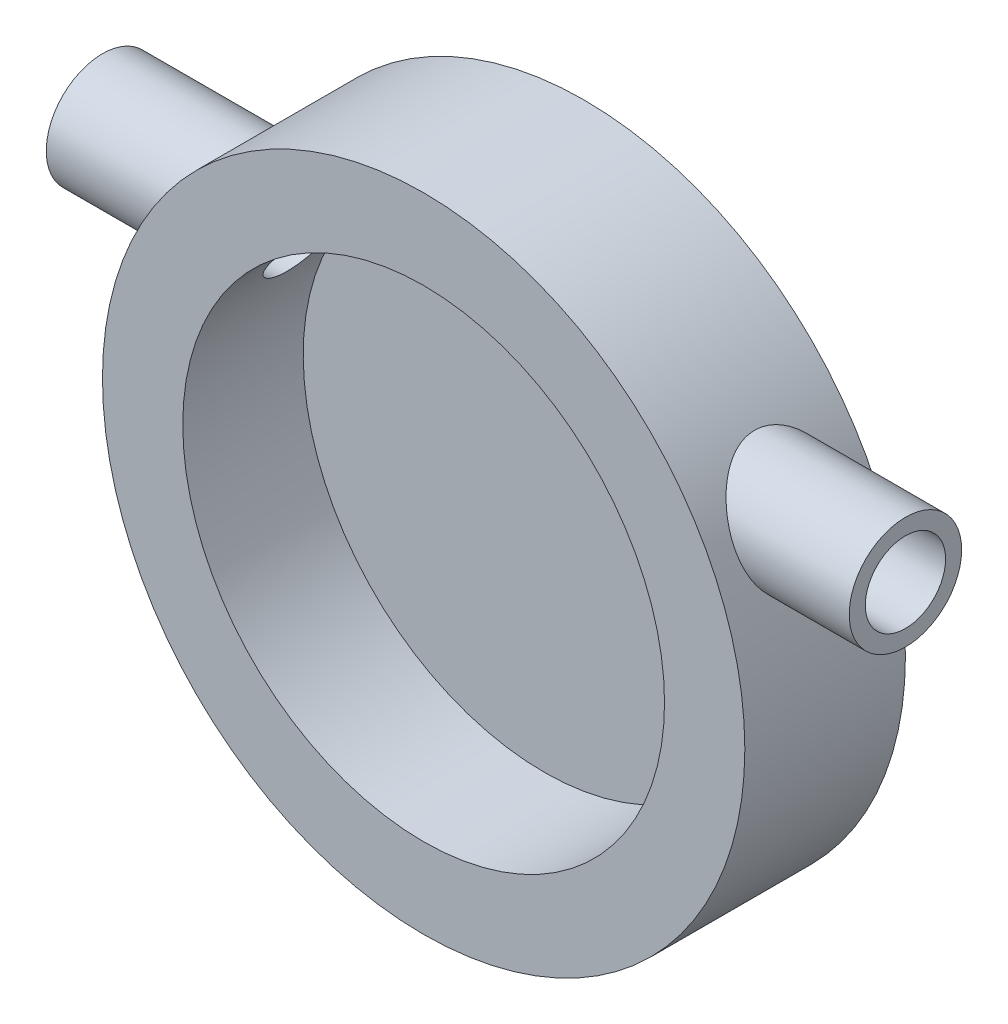
SolidWorks part; units mm, degrees
ref_plane "Front Plane" through (0, 0, 0) normal (0, 0, 1) x (1, 0, 0)
ref_plane "Top Plane" through (0, 0, 0) normal (0, 1, 0) x (1, 0, 0)
ref_plane "Right Plane" through (0, 0, 0) normal (1, 0, 0) x (0, 0, -1)
sketch "Sketch1" plane through (0, 0, 0) normal (0, 0, 1) x (1, 0, 0)
  circle A0 centre (0, 0) radius 40
extrude "Boss-Extrude1" add sketch "Sketch1" against normal blind 20
sketch "Sketch3" plane through (0, 0, 0) normal (1, 0, 0) x (0, 0, -1)
  line L0 (0, 40) -> (0, -40) construction
  circle A0 centre (10, 18) radius 7
  dimension "D1" = 10
  dimension "D3" = 14
  dimension "D2" = 18
extrude "Boss-Extrude2" add sketch "Sketch3" along normal blind 50 and the other way blind 50
sketch "Sketch5" plane through (50, 0, 0) normal (1, 0, 0) x (0, 0, -1)
  circle A0 centre (10, 18) radius 5
  dimension "D1" = 10
extrude "Cut-Extrude2" cut sketch "Sketch5" against normal through all
sketch "Sketch2" plane through (0, 0, 0) normal (0, 0, 1) x (1, 0, 0)
  circle A0 centre (0, 0) radius 30
  dimension "D1" = 60
extrude "Cut-Extrude3" cut sketch "Sketch2" against normal blind 15
